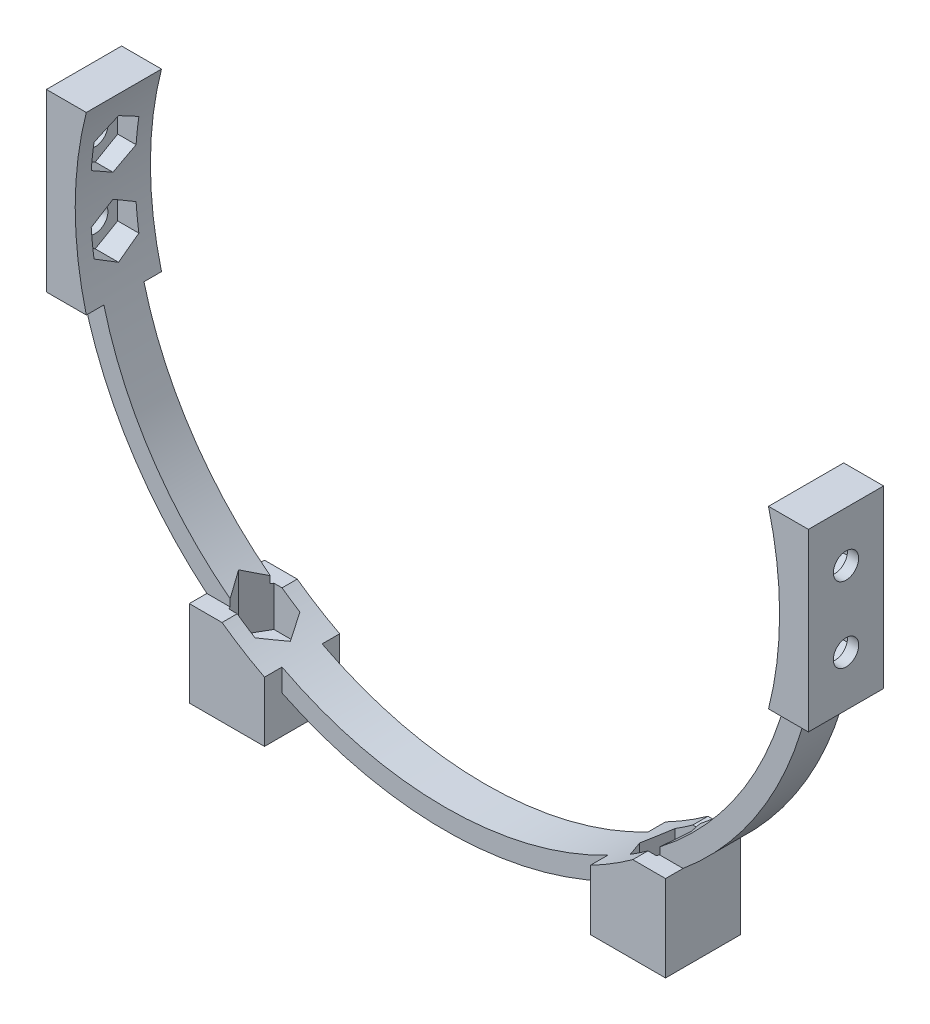
SolidWorks part; units mm, degrees
ref_plane "Front Plane" through (0, 0, 0) normal (0, 0, 1) x (1, 0, 0)
ref_plane "Top Plane" through (0, 0, 0) normal (0, 1, 0) x (1, 0, 0)
ref_plane "Right Plane" through (0, 0, 0) normal (1, 0, 0) x (0, 0, -1)
sketch "Sketch1" plane through (0, 0, 0) normal (0, 0, 1) x (1, 0, 0)
  line L1 (-76, 0) -> (-70.255, 0) construction
  line L2 (-70.255, 0) -> (70.255, 0) construction
  line L3 (76, 0) -> (74.255, 0) construction
  line L5 (-76, 0) -> (-76, -17.5)
  line L6 (-76, 0) -> (-76, 17.5)
  line L7 (-76, 17.5) -> (-70.255, 17.5)
  line L8 (-70.255, 17.5) -> (-70.255, 0) construction
  line L9 (-76, -17.5) -> (-72.1634, -17.5)
  line L11 (0, 0) -> (0, -70.255) construction
  line L12 (70.255, 17.5) -> (70.255, 0) construction
  line L13 (76, 17.5) -> (70.255, 17.5)
  line L14 (76, 0) -> (76, 17.5)
  line L15 (76, 0) -> (76, -17.5)
  line L16 (76, -17.5) -> (72.1634, -17.5)
  line L17 (70.255, 0) -> (76, 0) construction
  line L18 (-70.255, 17.5) -> (-68.0405, 17.5)
  line L19 (-68.0405, 17.5) -> (68.0405, 17.5) construction
  line L20 (68.0405, 17.5) -> (70.255, 17.5)
  line L21 (-72.1634, -17.5) -> (-68.0405, -17.5)
  line L22 (-68.0405, -17.5) -> (68.0405, -17.5) construction
  line L23 (68.0405, -17.5) -> (72.1634, -17.5)
  arc A0 (-70.255, 0) -> (70.255, 0) centre (0, 0) ccw
  arc A1 (-72.1634, -17.5) -> (72.1634, -17.5) centre (0, 0) ccw
  arc A2 (74.255, 0) -> (-74.255, 0) centre (0, 0) ccw construction
  arc A3 (68.0405, 17.5) -> (-68.0405, 17.5) centre (0, 0) ccw construction
  arc A4 (-74.255, 0) -> (-73.7302, -8.8123) centre (0, 0) ccw construction
  arc A5 (-73.7302, -8.8123) -> (-72.1634, -17.5) centre (0, 0) ccw construction
  arc A6 (73.7302, -8.8123) -> (74.255, 0) centre (0, 0) ccw construction
  arc A7 (72.1634, -17.5) -> (73.7302, -8.8123) centre (0, 0) ccw construction
  arc A8 (-68.0405, 17.5) -> (-70.255, 0) centre (0, 0) ccw
  arc A9 (70.255, 0) -> (68.0405, 17.5) centre (0, 0) ccw
  point P12 (-73.1275, 17.5)
  dimension "D1" = 140.51
  dimension "D2" = 4
  dimension "D3" = 76
  dimension "D4" = 35
extrude "Boss-Extrude1" add sketch "Sketch1" along normal mid plane 8 contours A8 L18 L7 L6 L5 L9 L21 A0 | L21 A1 L23 A0 | A9 A0 L23 L16 L15 L14 L13 L20 region at (-72.7273, 0, 0) region at (-70.102, -19.0508, 0) region at (72.7273, 0, 0)
ref_plane "Plane1" through (70.255, 0, 0) normal (-1, 0, 0) x (0, 0, 1)
extrude "Boss-Extrude2" add sketch "Sketch1<5>" along normal mid plane 15 contours A8 L18 L7 L6 L5 L9 L21 A0 | A9 A0 L23 L16 L15 L14 L13 L20 region at (-72.7273, 0, 0) region at (72.7273, 0, 0)
sketch "Sketch1<5>" plane through (0, 0, 0) normal (0, 0, 1) x (1, 0, 0) same geometry as "Sketch1"
sketch "Sketch2" plane through (70.255, 0, 0) normal (-1, 0, 0) x (0, 0, 1)
  line L0 (-7.5, 0) -> (7.5, 0) construction
  line L3 (0, 0) -> (0, 7.5) construction
  line L4 (0, 0) -> (0, -7.5) construction
  line L5 (-7.5, 17.5) -> (-7.5, -17.5) construction
  line L6 (0, 2.3327) -> (4.475, 4.9164)
  line L7 (4.475, 4.9164) -> (4.475, 10.0836)
  line L8 (4.475, 10.0836) -> (0, 12.6673)
  line L9 (0, 12.6673) -> (-4.475, 10.0836)
  line L10 (-4.475, 10.0836) -> (-4.475, 4.9164)
  line L11 (-4.475, 4.9164) -> (0, 2.3327)
  line L12 (0, -12.6673) -> (4.475, -10.0836)
  line L13 (4.475, -10.0836) -> (4.475, -4.9164)
  line L14 (4.475, -4.9164) -> (0, -2.3327)
  line L15 (0, -2.3327) -> (-4.475, -4.9164)
  line L16 (-4.475, -4.9164) -> (-4.475, -10.0836)
  line L17 (-4.475, -10.0836) -> (0, -12.6673)
  line L18 (7.5, -17.5) -> (7.5, 17.5) construction
  circle A0 centre (0, 7.5) radius 4.475 construction
  circle A1 centre (0, -7.5) radius 4.475 construction
  point P5 (0, -7.5)
  point P32 (0, 7.5)
  dimension "D1" = 8.95
  dimension "D2" = 15
extrude "Cut-Extrude1" cut sketch "Sketch2" against normal blind 3.5 and the other way blind 3.5
hole_wizard "#8 (0.199) Diameter Hole1" positions "3DSketch1" profile "Sketch4" hole size "#8" standard "ANSI Inch"
sketch3d "3DSketch1"
  point P0 (76, 7.5, 0)
  point P2 (76, -7.5, 0)
sketch "Sketch4" plane through (76, 7.5, 0) normal (0, 1, 0) x (0, 0, -1)
  line L0 (0, 0) -> (0, 10.71)
  line L1 (0, 10.71) -> (2.5273, 9.1914)
  line L2 (2.5273, 9.1914) -> (2.5273, 0)
  line L5 (2.5273, 0) -> (0, 0)
  line L10 (0, 10.71) -> (-2.5273, 9.1914) construction
  line L11 (0, -6.35) -> (0, 107.95) construction
  dimension "Hole Dia." = 5.0546
  dimension "Hole Depth" = 10.71
  dimension "Drill Angle" = 118
mirror "Mirror1" about plane through (0, 0, 0) normal (1, 0, 0) of "#8 (0.199) Diameter Hole1", "Cut-Extrude1"
sketch "Sketch5" plane through (0, 0, 0) normal (0, 0, 1) x (1, 0, 0)
  line L0 (-47.5, -57.075) -> (47.5, -57.075) construction
  line L1 (47.5, -57.075) -> (47.5, -74.255)
  line L2 (47.5, -74.255) -> (32.5, -74.255)
  line L3 (-32.5, -74.255) -> (-47.5, -74.255)
  line L4 (-47.5, -74.255) -> (-47.5, -57.075)
  line L5 (-47.5, -62.2858) -> (-32.5, -62.2858) construction
  line L6 (-32.5, -62.2858) -> (-32.5, -74.255)
  line L7 (-47.5, -57.075) -> (-40.966, -57.075)
  line L8 (32.5, -74.255) -> (32.5, -62.2858)
  line L9 (47.5, -57.075) -> (40.966, -57.075)
  line L10 (0, -74.255) -> (-32.5, -74.255) construction
  line L11 (32.5, -74.255) -> (0, -74.255) construction
  arc A0 (-72.1634, -17.5) -> (72.1634, -17.5) centre (0, 0) ccw construction
  arc A1 (-68.0405, -17.5) -> (68.0405, -17.5) centre (0, 0) ccw construction
  arc A2 (-40.966, -57.075) -> (-32.5, -62.2858) centre (0, 0) ccw
  arc A3 (-68.0405, -17.5) -> (-40.966, -57.075) centre (0, 0) ccw construction
  arc A4 (32.5, -62.2858) -> (40.966, -57.075) centre (0, 0) ccw
  arc A5 (-32.5, -62.2858) -> (32.5, -62.2858) centre (0, 0) ccw construction
  arc A6 (40.966, -57.075) -> (68.0405, -17.5) centre (0, 0) ccw construction
  dimension "D1" = 95
  dimension "D2" = 15
extrude "Boss-Extrude3" add sketch "Sketch5" along normal up to surface and the other way up to surface up to face at (-72.5739, 0, 7.5) other way up to face at (-72.5739, 0, -7.5)
sketch "Sketch6" plane through (0, -57.075, 0) normal (0, 1, 0) x (1, 0, 0)
  line L0 (-47.5, 7.5) -> (-47.5, -7.5) construction
  line L1 (-47.5, -7.5) -> (47.5, -7.5) construction
  line L2 (47.5, -7.5) -> (47.5, 7.5) construction
  line L3 (47.5, 7.5) -> (-47.5, 7.5) construction
  line L4 (-32.5, 7.5) -> (-32.5, -7.5) construction
  line L5 (-32.5, -7.5) -> (32.5, -7.5) construction
  line L6 (32.5, -7.5) -> (32.5, 7.5) construction
  line L7 (-47.5, 0) -> (-32.5, 0) construction
  line L8 (-32.5, 0) -> (32.5, 0) construction
  line L9 (32.5, 0) -> (47.5, 0) construction
  line L11 (-37.4164, -4.475) -> (-34.8327, 0)
  line L12 (-34.8327, 0) -> (-37.4164, 4.475)
  line L13 (-37.4164, 4.475) -> (-42.5836, 4.475)
  line L14 (-42.5836, 4.475) -> (-45.1673, 0)
  line L15 (-45.1673, 0) -> (-42.5836, -4.475)
  line L16 (-42.5836, -4.475) -> (-37.4164, -4.475)
  line L17 (42.5836, -4.475) -> (45.1673, 0)
  line L18 (45.1673, 0) -> (42.5836, 4.475)
  line L19 (42.5836, 4.475) -> (37.4164, 4.475)
  line L20 (37.4164, 4.475) -> (34.8327, 0)
  line L21 (34.8327, 0) -> (37.4164, -4.475)
  line L22 (37.4164, -4.475) -> (42.5836, -4.475)
  circle A0 centre (-40, 0) radius 4.475 construction
  circle A1 centre (40, 0) radius 4.475 construction
  point P37 (40, 0)
  point P39 (-40, 0)
  dimension "D1" = 8.95
extrude "Cut-Extrude2" cut sketch "Sketch6" against normal blind 8 and the other way blind 3.5
hole_wizard "#8 (0.199) Diameter Hole2" positions "3DSketch2" profile "Sketch7" hole size "#8" standard "ANSI Inch"
sketch3d "3DSketch2"
  point P0 (-40, -74.255, 0)
  point P2 (40, -74.255, 0)
sketch "Sketch7" plane through (-40, -74.255, 0) normal (1, 0, 0) x (0, 0, -1)
  line L0 (0, 0) -> (0, 13)
  line L1 (0, 13) -> (2.5273, 11.4814)
  line L2 (2.5273, 11.4814) -> (2.5273, 0)
  line L5 (2.5273, 0) -> (0, 0)
  line L10 (0, 13) -> (-2.5273, 11.4814) construction
  line L11 (0, -6.35) -> (0, 107.95) construction
  dimension "Hole Dia." = 5.0546
  dimension "Hole Depth" = 13
  dimension "Drill Angle" = 118
